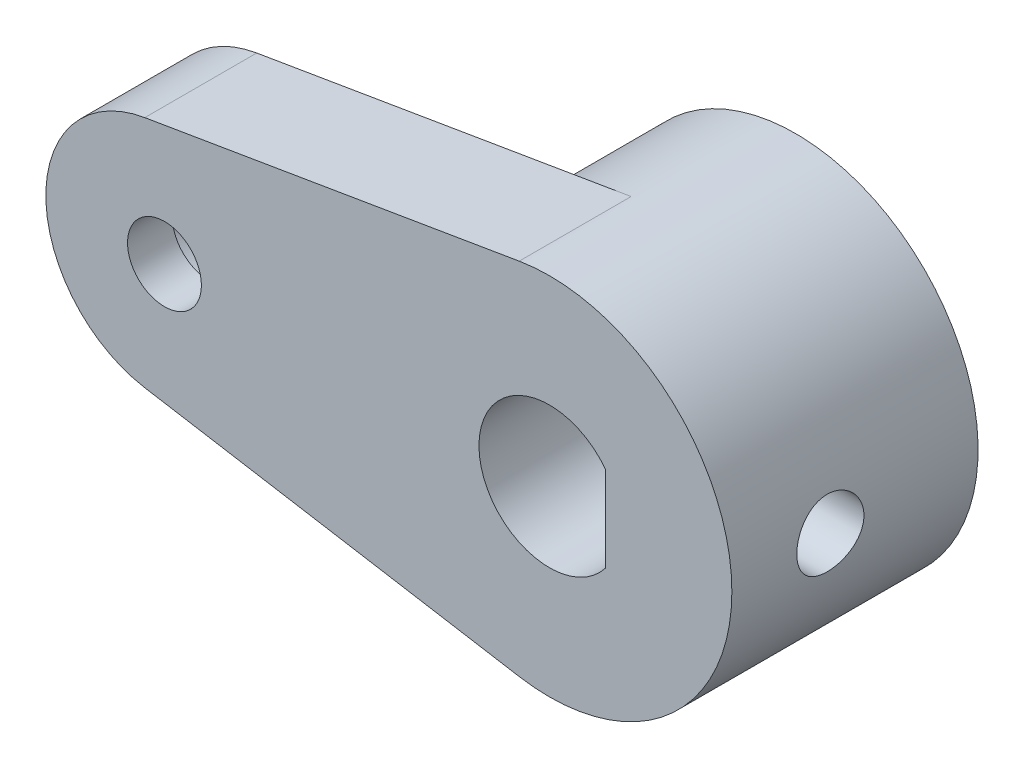
SolidWorks part; units mm, degrees
ref_plane "Front Plane" through (0, 0, 0) normal (0, 0, 1) x (1, 0, 0)
ref_plane "Top Plane" through (0, 0, 0) normal (0, 1, 0) x (1, 0, 0)
ref_plane "Right Plane" through (0, 0, 0) normal (1, 0, 0) x (0, 0, -1)
sketch "Sketch1" plane through (0, 0, 0) normal (0, 0, 1) x (1, 0, 0)
  line L0 (-12.05, 16) -> (-34.55, 16) construction
  line L1 (5.15, 16) -> (-12.05, 16) construction
  circle A0 centre (-12.05, 16) radius 22.5
  circle A1 centre (-12.05, 16) radius 3.15
  circle A2 centre (-29.25, 16) radius 1.65
  circle A3 centre (5.15, 16) radius 1.65
  dimension "D2" = 6.3
  dimension "D3" = 3.3
  dimension "D4" = 45
  dimension "D1" = 17.2
  dimension "D5" = 17.2
extrude "Boss-Extrude1" add sketch "Sketch1" along normal blind 2
sketch "Sketch2" plane through (0, 0, 0) normal (0, 0, -1) x (-1, 0, 0)
  circle A0 centre (12.05, 16) radius 3.15
  circle A1 centre (12.05, 16) radius 8.15
  circle A2 centre (12.05, 16) radius 3.15 construction
  dimension "D1" = 5
extrude "Boss-Extrude2" add sketch "Sketch2" along normal blind 9
sketch "Sketch3" plane through (0, 0, 2) normal (0, 0, 1) x (1, 0, 0)
  line L0 (-30.1282, 10.7733) -> (-13.4004, 7.9627)
  line L1 (-29.25, 16) -> (-23.95, 16) construction
  line L2 (-30.1282, 21.2267) -> (-13.4004, 24.0373)
  line L4 (19.6041, 50.5792) -> (-39.7177, 50.5792)
  line L5 (19.6041, 50.5792) -> (19.6041, -18.1222)
  line L6 (19.6041, -18.1222) -> (-39.7177, -18.1222)
  line L7 (-39.7177, 50.5792) -> (-39.7177, -18.1222)
  line L8 (19.6041, 50.5792) -> (-39.7177, -18.1222) construction
  line L9 (19.6041, -18.1222) -> (-39.7177, 50.5792) construction
  arc A0 (-30.1282, 21.2267) -> (-30.1282, 10.7733) centre (-29.25, 16) ccw
  arc A1 (-13.4004, 7.9627) -> (-13.4004, 24.0373) centre (-12.05, 16) ccw
  circle A2 centre (-12.05, 16) radius 22.5 construction
  point P17 (-10.0568, 16.2285)
  dimension "D1" = 8.15
extrude "Cut-Extrude1" cut sketch "Sketch3" against normal through all both
sketch "Sketch7" plane through (0, 0, 2) normal (0, 0, 1) x (1, 0, 0)
  line L0 (-8.9664, 16) -> (-30.9, 16) construction
  line L1 (-9.55, 17.9164) -> (-8.3827, 17.9164)
  line L2 (-9.55, 17.9164) -> (-9.55, 14.0836)
  line L3 (-9.55, 14.0836) -> (-8.3827, 14.0836)
  line L4 (-8.3827, 17.9164) -> (-8.3827, 14.0836)
  line L5 (-9.55, 17.9164) -> (-8.3827, 14.0836) construction
  line L6 (-9.55, 14.0836) -> (-8.3827, 17.9164) construction
  line L7 (-15.2, 16) -> (-15.2, 20.2929) construction
  circle A0 centre (-12.05, 16) radius 3.15 construction
  circle A1 centre (-29.25, 16) radius 1.65 construction
  point P4 (-8.9664, 16)
  dimension "D1" = 5.65
extrude "Boss-Extrude4" add sketch "Sketch7" against normal up to surface (11 mm away) up to face at (-20.2, 16, -9)
sketch "Sketch4" plane through (0, 0, 0) normal (1, 0, 0) x (0, 0, -1)
  line L0 (2.4012, 16) -> (-2, 16) construction
  line L1 (-0.5, 17.675) -> (-0.5, 14.325)
  line L2 (-0.5, 14.325) -> (2.4012, 12.65)
  line L3 (2.4012, 12.65) -> (5.3024, 14.325)
  line L4 (5.3024, 14.325) -> (5.3024, 17.675)
  line L5 (5.3024, 17.675) -> (2.4012, 19.35)
  line L6 (2.4012, 19.35) -> (-0.5, 17.675)
  line L9 (-2, 24.15) -> (-2, 7.85) construction
  circle A0 centre (2.4012, 16) radius 2.9012 construction
  dimension "D1" = 3.35
  dimension "D2" = 1.5
extrude "Cut-Extrude2" cut sketch "Sketch4" along normal blind 2.8 and the other way blind 2 from surface starting at face at (-9.55, 16, -3.5)
sketch "Sketch5" plane through (-11.55, 0, 0) normal (-1, 0, 0) x (0, 0, 1)
  line L0 (-5.3024, 14.325) -> (0.5, 17.675) construction
  circle A0 centre (-2.4012, 16) radius 1.5
  point P7 (-2.4012, 16)
  dimension "D1" = 3
extrude "Cut-Extrude3" cut sketch "Sketch5" against normal through all
sketch "Sketch6" plane through (0, 0, 0) normal (0, 0, -1) x (-1, 0, 0)
  line L2 (30.1282, 21.2267) -> (13.4004, 24.0373)
  line L3 (13.4004, 7.9627) -> (30.1282, 10.7733)
  line L4 (30.1282, 21.2267) -> (13.4004, 24.0373)
  line L5 (13.4004, 7.9627) -> (30.1282, 10.7733)
  circle A0 centre (29.25, 16) radius 2.9
  arc A2 (13.4004, 7.9627) -> (13.4004, 24.0373) centre (12.05, 16) ccw
  arc A3 (30.1282, 10.7733) -> (30.1282, 21.2267) centre (29.25, 16) ccw
  arc A4 (13.4004, 7.9627) -> (13.4004, 24.0373) centre (12.05, 16) ccw
  arc A5 (30.1282, 10.7733) -> (30.1282, 21.2267) centre (29.25, 16) ccw
  dimension "D2" = 5.8
  dimension "D1" = 0
extrude "Boss-Extrude3" add sketch "Sketch6" along normal blind 3
